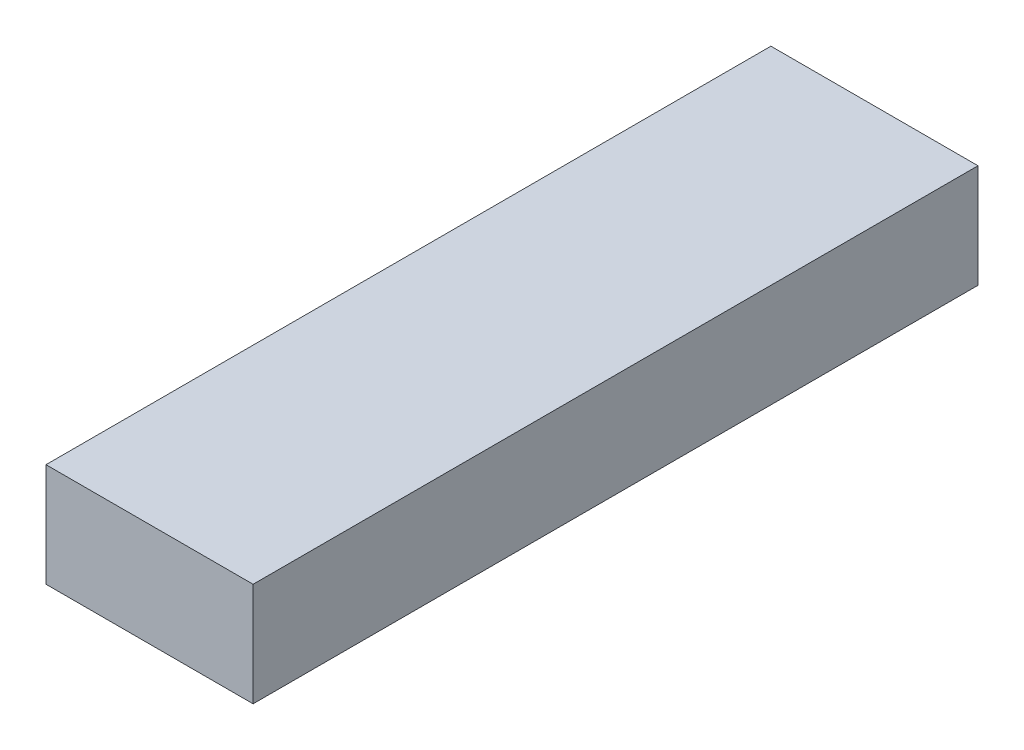
SolidWorks part; units mm, degrees
material "POLYURETHANE (11671)"
ref_plane "Front Plane" through (0, 0, 0) normal (0, 0, 1) x (1, 0, 0)
ref_plane "Top Plane" through (0, 0, 0) normal (0, 1, 0) x (1, 0, 0)
ref_plane "Right Plane" through (0, 0, 0) normal (1, 0, 0) x (0, 0, -1)
sketch "Sketch1" plane through (0, 0, 0) normal (0, 1, 0) x (1, 0, 0)
  line L1 (0, 0) -> (6.35, 0)
  line L2 (0, 0) -> (0, 22.225)
  line L3 (0, 22.225) -> (6.35, 22.225)
  line L4 (6.35, 0) -> (6.35, 22.225)
  dimension "D1" = 6.35
  dimension "D2" = 22.225
extrude "Boss-Extrude1" add sketch "Sketch1" along normal blind 3.175
